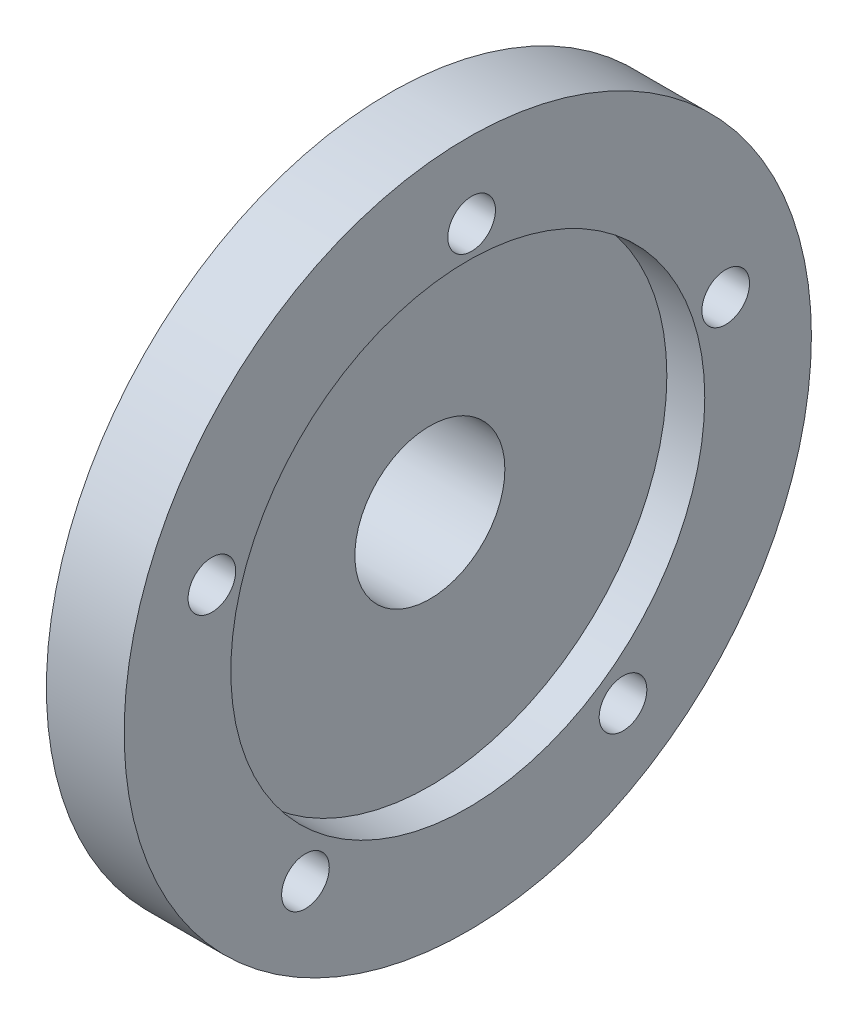
SolidWorks part; units mm, degrees
material "6061 Alloy"
ref_plane "Front Plane" through (0, 0, 0) normal (0, 0, 1) x (1, 0, 0)
ref_plane "Top Plane" through (0, 0, 0) normal (0, 1, 0) x (1, 0, 0)
ref_plane "Right Plane" through (0, 0, 0) normal (1, 0, 0) x (0, 0, -1)
sketch "Sketch1" plane through (0, 0, 0) normal (0, 0, 1) x (1, 0, 0)
  line L0 (0, 0) -> (-647.0721, 0) construction
  line L1 (-27.8573, 8.0391) -> (-14.0241, 8.0391)
  line L2 (-14.0241, 8.0391) -> (-14.0241, 25.4)
  line L3 (-14.0241, 25.4) -> (-9.9601, 25.4)
  line L5 (-18.2958, 17.8013) -> (-27.8573, 17.8013) construction
  line L6 (-27.8573, 17.8013) -> (-27.8573, 8.0391)
  line L7 (-9.9601, 25.4) -> (-9.9601, 36.83)
  line L8 (-9.9601, 36.83) -> (-18.2958, 36.83)
  line L10 (-12.8446, -23.9061) -> (-22.4061, -23.9061) construction
  line L11 (-4.5089, -34.3169) -> (-12.8446, -34.3169) construction
  line L12 (-18.2958, 36.83) -> (-27.8573, 17.8013)
  dimension "D1" = 16.0782
  dimension "D2" = 50.8
  dimension "D3" = 4.064
  dimension "D4" = 73.66
revolve "Revolve1" add sketch "Sketch1" angle 360 about L0
sketch "Sketch2" plane through (-9.9601, 0, 0) normal (1, 0, 0) x (0, 0, -1)
  circle A0 centre (27.6444, 8.2049) radius 2.032 construction
  circle A1 centre (0.4111, 28.6268) radius 2.032 construction
  circle A2 centre (-27.4269, 9.0372) radius 2.032 construction
  circle A3 centre (-17.3985, -23.4919) radius 2.032 construction
  circle A4 centre (16.6374, -24.0063) radius 2.032 construction
  circle A5 centre (27.6444, 8.2049) radius 2.032 construction
  circle A6 centre (0.4111, 28.6268) radius 2.032 construction
  circle A7 centre (-27.4269, 9.0372) radius 2.032 construction
  circle A8 centre (-17.3985, -23.4919) radius 2.032 construction
  circle A9 centre (16.6374, -24.0063) radius 2.032 construction
  circle A10 centre (16.6374, -24.0063) radius 2.5527
  circle A11 centre (-17.3985, -23.4919) radius 2.5527
  circle A12 centre (0.4111, 28.6268) radius 2.5527
  circle A13 centre (27.6444, 8.2049) radius 2.5527
  circle A14 centre (-27.4269, 9.0372) radius 2.5527
  dimension "D1" = 5.1054
extrude "Cut-Extrude1" cut sketch "Sketch2" against normal through all
